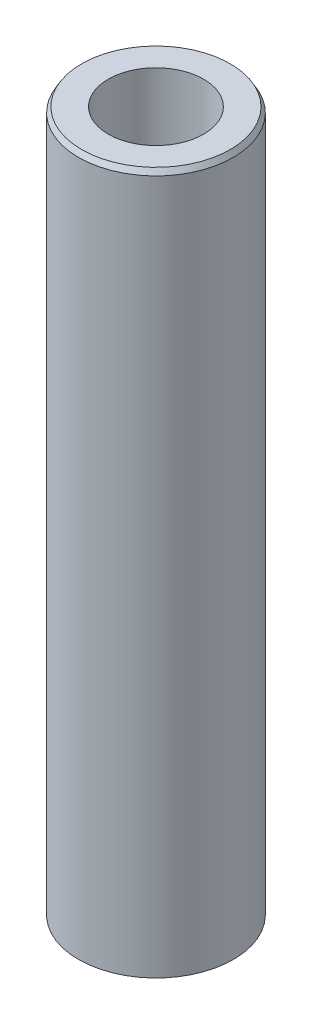
SolidWorks part; units mm, degrees
ref_plane "Front Plane" through (0, 0, 0) normal (0, 0, 1) x (1, 0, 0)
ref_plane "Top Plane" through (0, 0, 0) normal (0, 1, 0) x (1, 0, 0)
ref_plane "Right Plane" through (0, 0, 0) normal (1, 0, 0) x (0, 0, -1)
sketch "Sketch1" plane through (0, 0, 0) normal (0, 1, 0) x (1, 0, 0)
  circle A0 centre (0, 0) radius 10
  dimension "SHAFT_OD" = 20
extrude "Boss-Extrude1" add sketch "Sketch1" along normal blind 90.8574
sketch "Sketch2" plane through (0, 0, 0) normal (0, 1, 0) x (1, 0, 0)
  circle A0 centre (0, 0) radius 6.1634
  dimension "BORE_D" = 12.3267
extrude "Cut-Extrude1" cut sketch "Sketch2" along normal through all
chamfer "Chamfer1" distance 0.6839 angle 30 2 edges at (0, 90.8574, 10) (0, 0, 10) first distance on face at (0, 90.8574, 10) first distance on face at (0, 0, 6.1634)
